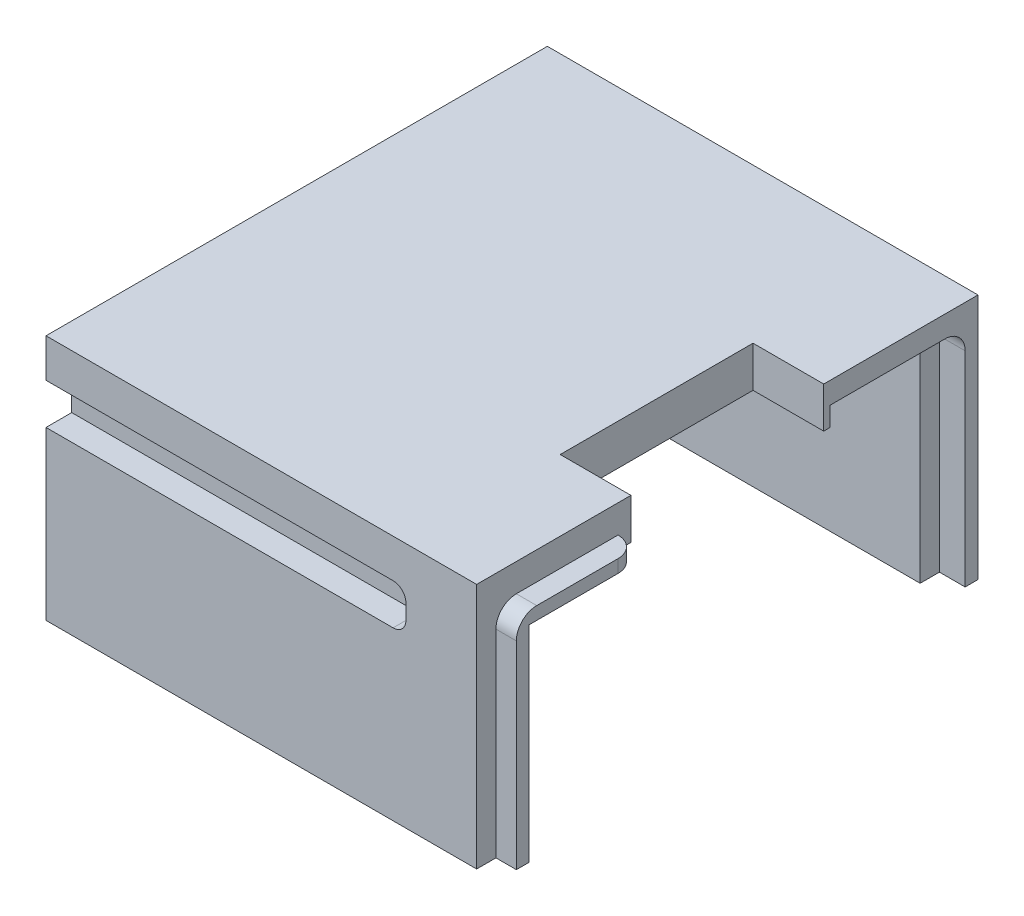
SolidWorks part; units mm, degrees
material "Copper"
ref_plane "Front Plane" through (0, 0, 0) normal (0, 0, 1) x (1, 0, 0)
ref_plane "Top Plane" through (0, 0, 0) normal (0, 1, 0) x (1, 0, 0)
ref_plane "Right Plane" through (0, 0, 0) normal (1, 0, 0) x (0, 0, -1)
sketch "MainSketch" plane through (0, 0, 0) normal (0, 1, 0) x (1, 0, 0)
  line L0 (0, -2.5) -> (-31, -2.5)
  line L1 (0, 0) -> (-33.5, 0)
  line L2 (0, 0) -> (0, -39)
  line L3 (0, -39) -> (-33.5, -39)
  line L4 (-33.5, 0) -> (-33.5, -39)
  line L5 (-31, -2.5) -> (-31, -36.5)
  line L6 (-31, -36.5) -> (0, -36.5)
  line L7 (30.5, -3) -> (-30.5, -3) construction
  line L8 (-30.5, -3) -> (-30.5, -36) construction
  line L9 (-30.5, -36) -> (30.5, -36) construction
  line L13 (-5.5, -12) -> (5.5, -12)
  line L14 (-5.5, -12) -> (-5.5, -27)
  line L15 (-5.5, -27) -> (5.5, -27)
  line L16 (5.5, -12) -> (5.5, -27)
  point P7 (-10, -1.25)
  point P10 (-32, -1.25)
  point P11 (-32, -37.75)
  point P12 (-10, -37.75)
  point P21 (5.5, -19.5)
  point P22 (0, -19.5)
  point P23 (0, -12)
  point P24 (-16.75, -1.25)
  point P26 (-16.75, -37.75)
  dimension "D1" = 2.5
  dimension "D2" = 2.5
  dimension "D3" = 2.5
  dimension "D4" = 33.5
  dimension "D6" = 3
  dimension "D7" = 3
  dimension "D8" = 3
  dimension "D9" = 1.5
  dimension "D11" = 10
  dimension "D12" = 10
  dimension "D13" = 1.25
  dimension "D5" = 33
  dimension "D16" = 61
  dimension "D17" = 16.75
  dimension "D14" = 11
  dimension "D15" = 15
  dimension "D18" = 2.5
  dimension "D10" = 1.25
extrude "Wall" add sketch "MainSketch" along normal blind 16 contours L6 L5 L0 L2 L1 L4 L3 region at (-15.5, 0, 1.9859)
extrude "Roof" add sketch "MainSketch<3>" along normal blind 3.175 from surface contours L5 L6 L2 L0 | L6 L5 L0 L2 L1 L4 L3 region at (-16.5827, 0, 19.5) region at (-15.5, 0, 1.9859) starting at face at (-16.125, 16, 19.5)
sketch "MainSketch<3>" plane through (0, 0, 0) normal (0, 1, 0) x (1, 0, 0) same geometry as "MainSketch"
hole_wizard "#2-56 Tapped Hole1" positions "3DSketch1" profile "Sketch2" tap size "#2-56" standard "ANSI Inch"
sketch3d "3DSketch1"
  point P19 (-16.75, 0, 37.75)
  point P22 (-16.75, 0, 1.25)
sketch "Sketch2" plane through (-16.75, 0, 37.75) normal (1, 0, 0) x (0, 0, -1)
  line L0 (0, 0) -> (0, 6.2642)
  line L1 (0, 6.2642) -> (0.889, 5.73)
  line L2 (0.889, 5.73) -> (0.889, 0)
  line L5 (0.889, 0) -> (0, 0)
  line L10 (0, 6.2642) -> (-0.889, 5.73) construction
  line L11 (0, -6.35) -> (0, 107.95) construction
  dimension "Tap Drill Dia." = 1.778
  dimension "Tap Drill Depth" = 5.73
  dimension "Drill Angle" = 118
cosmetic thread "Hole Thread1" parameters "D1"=4.37, "D2"=2.1844
cosmetic thread "Hole Thread2" parameters "D1"=4.37, "D2"=2.1844
sketch "Sketch3" plane through (0, 0, 0) normal (1, 0, 0) x (0, 0, -1)
  line L0 (-37.5, 0) -> (-37.5, 17)
  line L1 (-36.5, 0) -> (-39, 0) construction
  line L2 (-37.5, 17) -> (-28, 17)
  line L3 (-1, 17.5) -> (-1, 0)
  line L4 (0, 0) -> (-2.5, 0) construction
  line L5 (-36.5, 0) -> (-36.5, 16)
  line L6 (-36.5, 16) -> (-28, 16)
  line L7 (-2.5, 16) -> (-2.5, 0)
  line L8 (-37.5, 0) -> (-36.5, 0) construction
  line L10 (-2.5, 0) -> (-1, 0)
  line L11 (-11.5, 17.5) -> (-1, 17.5)
  line L12 (-11.5, 16) -> (-11.5, 17.5)
  line L15 (-37.5, 0) -> (-36.5, 0)
  line L16 (-28, 17) -> (-28, 16)
  line L18 (-11.5, 16) -> (-2.5, 16)
  line L22 (-27, 19.175) -> (-27, 16) construction
  line L23 (-12, 19.175) -> (-12, 16) construction
  line L24 (-2.5, 16) -> (-36.5, 16) construction
  line L25 (-2.5, 16) -> (-2.5, 0) construction
  line L26 (-36.5, 16) -> (-36.5, 0) construction
  dimension "D2" = 1
  dimension "D3" = 1
  dimension "D6" = 1.5
  dimension "D8" = 1.5
  dimension "D7" = 1
  dimension "D9" = 0.5
extrude "Boss-Extrude1" add sketch "Sketch3" along normal blind 1.5875 contours L16 L2 L0 L15 L5 L6 region at (0, 8.5, 37.3053)
extrude "Cut-Extrude3" cut sketch "Sketch3<3>" against normal blind 2 contours L12 L18 L7 L10 L3 L11 region at (0, 8.75, 1.2041)
sketch "Sketch3<3>" plane through (0, 0, 0) normal (1, 0, 0) x (0, 0, -1) same geometry as "Sketch3"
fillet "Fillet1" radius 1.5875 4 edges at (0.7937, 17, 37.5) (1.5875, 16.5, 28) (-1, 17.5, 1) (-2, 16.75, 11.5)
sketch "Sketch4" plane through (-33.5, 0, 0) normal (-1, 0, 0) x (0, 0, 1)
  line L0 (0, 19.175) -> (0, 0) construction
  line L1 (0, 16.175) -> (2, 16.175)
  line L2 (0, 16.175) -> (0, 13)
  line L3 (0, 13) -> (2, 13)
  line L4 (2, 16.175) -> (2, 13)
  line L5 (39, 19.175) -> (39, 0) construction
  line L6 (39, 16.175) -> (37, 16.175)
  line L7 (39, 16.175) -> (39, 13)
  line L8 (39, 13) -> (37, 13)
  line L9 (37, 16.175) -> (37, 13)
  line L10 (39, 19.175) -> (0, 19.175) construction
  dimension "D1" = 3.175
  dimension "D2" = 2
  dimension "D3" = 3
extrude "rail cut" cut sketch "Sketch4" against normal up to surface (28 mm away) and the other way through all up to face at (-5.5, 17.5875, 19.5)
fillet "Fillet2" radius 1 6 edges at (-31, 8, 36.5) (-31, 8, 2.5) (-5.5, 16.175, 38) (-5.5, 13, 38) (-5.5, 13, 1) (-5.5, 16.175, 1)
equation "\"D2@MainSketch\" = \"D1@MainSketch\""
equation "\"D3@MainSketch\" = \"D2@MainSketch\""
equation "\"D7@MainSketch\" = \"D6@MainSketch\""
equation "\"D8@MainSketch\" = \"D6@MainSketch\""
equation "\"D9@MainSketch\" = \"D7@MainSketch\" / 2"
equation "\"D12@MainSketch\" = \"D11@MainSketch\""
equation "\"D13@MainSketch\" = \"D10@MainSketch\""
equation "\"D4@MainSketch\"=(\"D16@MainSketch\"+\"D6@MainSketch\"*2)/2"
equation "\"side_thick\"=2.5"
equation "\"D1@MainSketch\"=\"side_thick\""
equation "\"top_thick\"=3.175"
equation "\"D1@Roof\"=\"top_thick\""
equation "\"D17@MainSketch\"=\"D4@MainSketch\"/2"
equation "\"D3@Sketch3\"=\"D2@Sketch3\""
equation "\"D8@Sketch3\"=\"D6@Sketch3\""
equation "\"D2@Sketch4\"=2"
equation "\"D10@MainSketch\"=\"D18@MainSketch\"/2"
